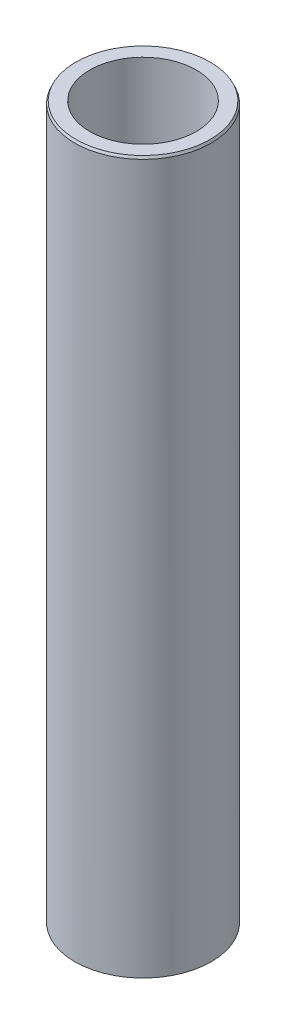
SolidWorks part; units mm, degrees
ref_plane "Front Plane" through (0, 0, 0) normal (0, 0, 1) x (1, 0, 0)
ref_plane "Top Plane" through (0, 0, 0) normal (0, 1, 0) x (1, 0, 0)
ref_plane "Right Plane" through (0, 0, 0) normal (1, 0, 0) x (0, 0, -1)
sketch "Sketch1" plane through (0, 0, 0) normal (0, 1, 0) x (1, 0, 0)
  circle A0 centre (0, 0) radius 57.5
  dimension "SHAFT_OD" = 115
extrude "Boss-Extrude1" add sketch "Sketch1" along normal blind 600
sketch "Sketch2" plane through (0, 0, 0) normal (0, 1, 0) x (1, 0, 0)
  circle A0 centre (0, 0) radius 44.8925
  dimension "BORE_D" = 89.7851
extrude "Cut-Extrude1" cut sketch "Sketch2" along normal through all
chamfer "Chamfer1" distance 2.1331 angle 25.155 2 edges at (0, 600, 57.5) (0, 0, 57.5) first distance on face at (0, 600, 57.5) first distance on face at (0, 0, 44.8925)
